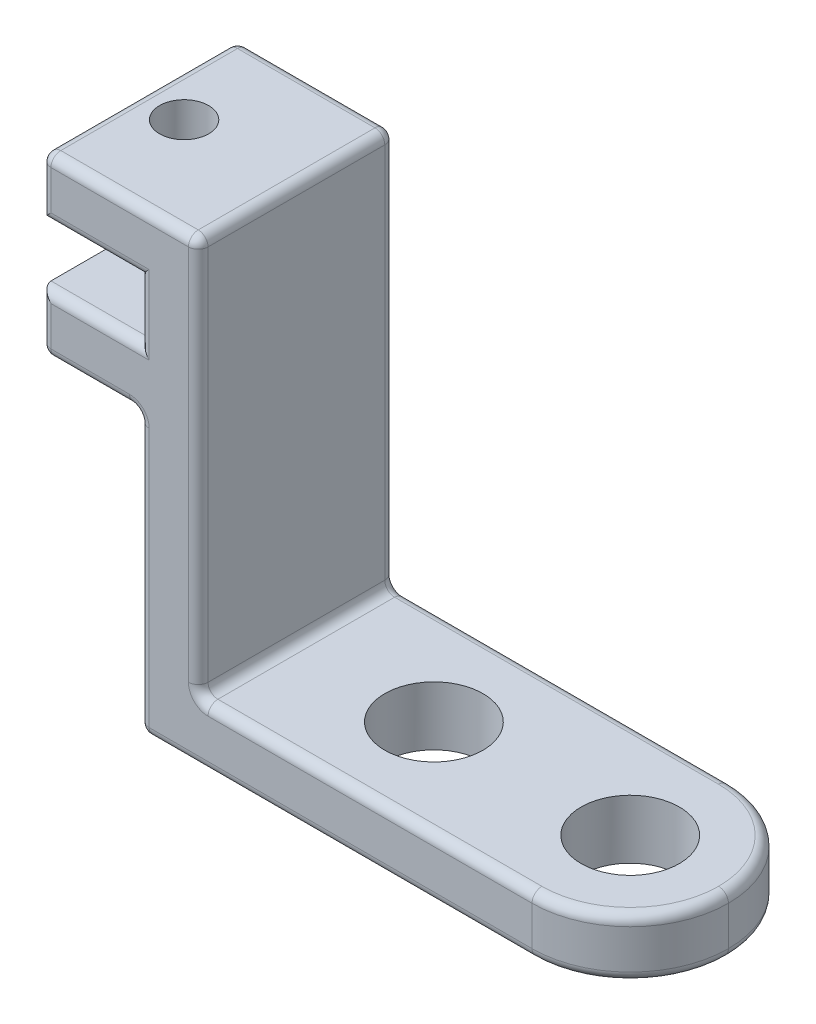
SolidWorks part; units mm, degrees
ref_plane "Front Plane" through (0, 0, 0) normal (0, 0, 1) x (1, 0, 0)
ref_plane "Top Plane" through (0, 0, 0) normal (0, 1, 0) x (1, 0, 0)
ref_plane "Right Plane" through (0, 0, 0) normal (1, 0, 0) x (0, 0, -1)
sketch "Sketch1" plane through (0, 0, 0) normal (0, 0, 1) x (1, 0, 0)
  line L0 (0, 0) -> (8, 0)
  line L1 (8, 0) -> (8, -20.2)
  line L2 (8, -20.2) -> (30, -20.2)
  line L3 (30, -20.2) -> (30, -23.2)
  line L4 (30, -23.2) -> (5, -23.2)
  line L5 (5, -23.2) -> (5, -9)
  line L6 (5, -9) -> (0, -9)
  line L7 (0, -9) -> (0, -6)
  line L8 (0, -6) -> (5, -6)
  line L9 (5, -6) -> (5, -3)
  line L10 (5, -3) -> (0, -3)
  line L11 (0, -3) -> (0, 0)
  dimension "D1" = 3
  dimension "D2" = 3
  dimension "D3" = 3
  dimension "D4" = 3
  dimension "D5" = 3
  dimension "D6" = 3
  dimension "D7" = 23.2
  dimension "D8" = 25
  dimension "D9" = 8
  dimension "D10" = 22
extrude "Boss-Extrude1" add sketch "Sketch1" along normal blind 10
sketch "Sketch2" plane through (0, 0, 0) normal (0, 1, 0) x (1, 0, 0)
  line L0 (0, -10) -> (0, 0) construction
  line L1 (8, 0) -> (0, 0) construction
  circle A0 centre (2.28, -5) radius 1.25
  dimension "D1" = 2.5
  dimension "D2" = 2.28
  dimension "D3" = 5
extrude "Cut-Extrude1" cut sketch "Sketch2" against normal through all
sketch "Sketch3" plane through (0, -20.2, 0) normal (0, 1, 0) x (1, 0, 0)
  line L0 (30, -10) -> (30, 0) construction
  line L1 (30, -10) -> (8, -10) construction
  circle A0 centre (25, -5) radius 2.5
  circle A1 centre (15, -5) radius 2.5
  point P6 (30, -5)
  dimension "D1" = 5
  dimension "D2" = 5
  dimension "D3" = 5
  dimension "D4" = 5
  dimension "D5" = 15
  dimension "D6" = 5
extrude "Cut-Extrude2" cut sketch "Sketch3" against normal up to next
fillet "Fillet1" radius 0.5 30 edges at (2.5, -9, 10) (0, -7.5, 10) (2.5, -6, 10) (5, -4.5, 10) (2.5, -3, 10) (4, 0, 10) (0, 0, 5) (0, -1.5, 10) (4, 0, 0) (0, -1.5, 0) (2.5, -3, 0) (5, -4.5, 0) (2.5, -6, 0) (0, -7.5, 0) (2.5, -9, 0) (0, -9, 5) (5, -9, 5) (5, -23.2, 5) (5, -16.1, 10) (17.5, -23.2, 10) (8, 0, 5) (8, -10.1, 10) (5, -16.1, 0) (8, -10.1, 0) (8, -20.2, 5) (19, -20.2, 10) (17.5, -23.2, 0) (19, -20.2, 0) (30, -23.2, 5) (30, -20.2, 5)
fillet "Fillet2" radius 5 6 edges at (29.8536, -20.3464, 0.1464) (29.8536, -23.0536, 0.1464) (29.8536, -20.3464, 9.8536) (29.8536, -23.0536, 9.8536) (30, -21.7, 10) (30, -21.7, 0)
